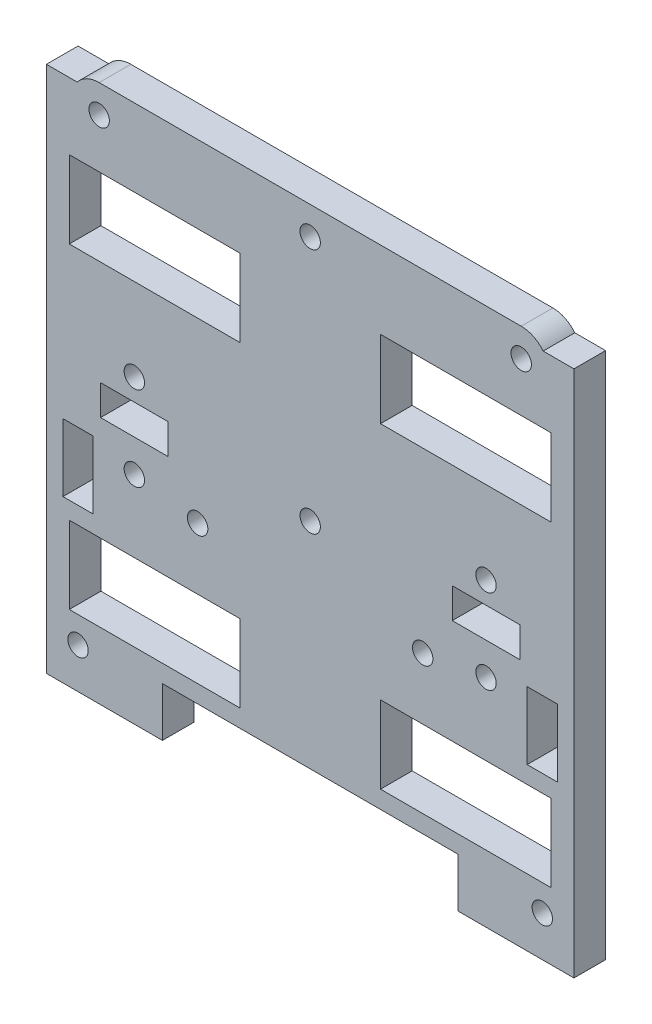
SolidWorks part; units mm, degrees
ref_plane "Front Plane" through (0, 0, 0) normal (0, 0, 1) x (1, 0, 0)
ref_plane "Top Plane" through (0, 0, 0) normal (0, 1, 0) x (1, 0, 0)
ref_plane "Right Plane" through (0, 0, 0) normal (1, 0, 0) x (0, 0, -1)
sketch "Sketch1" plane through (0, 0, 0) normal (0, 0, 1) x (1, 0, 0)
  line L0 (0, -37.5) -> (0, 37.5) construction
  line L1 (-47.5, -37.5) -> (47.5, -37.5)
  line L2 (-47.5, -37.5) -> (-47.5, 37.5)
  line L3 (-47.5, 37.5) -> (47.5, 37.5)
  line L4 (47.5, -37.5) -> (47.5, 37.5)
  line L5 (-47.5, -37.5) -> (47.5, 37.5) construction
  line L6 (-47.5, 37.5) -> (47.5, -37.5) construction
  line L7 (-47.5, 0) -> (47.5, 0) construction
  line L8 (-47.5, 22.5) -> (47.5, 22.5) construction
  line L9 (34.25, 17) -> (10, 28) construction
  line L10 (-34.25, 28) -> (-10, 28)
  line L11 (-34.25, 28) -> (-34.25, 17)
  line L12 (-34.25, 17) -> (-10, 17)
  line L13 (-10, 28) -> (-10, 17)
  line L14 (-34.25, 28) -> (-10, 17) construction
  line L15 (-34.25, 17) -> (-10, 28) construction
  line L16 (34.25, 28) -> (10, 17) construction
  line L17 (10, 28) -> (10, 17)
  line L18 (34.25, 17) -> (10, 17)
  line L19 (34.25, 28) -> (34.25, 17)
  line L20 (34.25, 28) -> (10, 28)
  line L21 (34.25, -28) -> (10, -17) construction
  line L22 (-34.25, -17) -> (-10, -28) construction
  line L23 (-34.25, -28) -> (-10, -17) construction
  line L24 (34.25, -17) -> (10, -28) construction
  line L25 (34.25, -28) -> (10, -28)
  line L26 (34.25, -28) -> (34.25, -17)
  line L27 (34.25, -17) -> (10, -17)
  line L28 (10, -28) -> (10, -17)
  line L29 (-10, -28) -> (-10, -17)
  line L30 (-34.25, -17) -> (-10, -17)
  line L31 (-34.25, -28) -> (-34.25, -17)
  line L32 (-34.25, -28) -> (-10, -28)
  point P0 (0, 0)
  point P12 (-22.125, 22.5)
  point P21 (22.125, 22.5)
  point P30 (22.125, -22.5)
  point P31 (-22.125, -22.5)
  dimension "D1" = 95
  dimension "D2" = 75
  dimension "D3" = 22.5
  dimension "D4" = 24.25
  dimension "D5" = 11
  dimension "D6" = 10
extrude "Boss-Extrude1" add sketch "Sketch1" along normal blind 4.5
sketch "Sketch8" plane through (0, 0, 4.5) normal (0, 0, 1) x (1, 0, 0)
  line L0 (-47.5, 37.5) -> (-47.5, -37.5) construction
  line L1 (47.5, -37.5) -> (47.5, 37.5) construction
  circle A0 centre (-47.5, 29.5) radius 8
  circle A1 centre (47.5, 29.5) radius 8
  dimension "D1" = 16
extrude "Boss-Extrude2" [suppressed] add sketch "Sketch8" against normal through all
sketch "Sketch2" plane through (0, 0, 4.5) normal (0, 0, 1) x (1, 0, 0)
  line L0 (0, -37.5) -> (0, 37.5) construction
  line L1 (-47.5, -37.5) -> (47.5, -37.5) construction
  line L2 (47.5, 37.5) -> (-47.5, 37.5) construction
  line L3 (-47.5, 0) -> (47.5, 0) construction
  line L4 (-47.5, 37.5) -> (-47.5, -37.5) construction
  line L5 (47.5, -37.5) -> (47.5, 37.5) construction
  line L6 (-40, 0) -> (40, 0) construction
  line L7 (-30, 35) -> (30, 35) construction
  circle A0 centre (-30, 35) radius 1.45
  circle A1 centre (30, 35) radius 1.45
  circle A2 centre (40, 0) radius 1.45
  circle A3 centre (-40, 0) radius 1.45
  circle A4 centre (0, 35) radius 1.45
  dimension "D1" = 2.9
  dimension "D7" = 2.9
  dimension "D8" = 2.9
  dimension "D9" = 2.9
  dimension "D2" = 30
  dimension "D3" = 35
  dimension "D4" = 80
  dimension "D5" = 40
  dimension "D6" = 0
extrude "screwHoles" cut sketch "Sketch2" against normal through all
sketch "Sketch3" plane through (0, 0, 4.5) normal (0, 0, 1) x (1, 0, 0)
  line L0 (-47.5, -20) -> (26.0486, -20) construction
  line L1 (-47.5, 37.5) -> (-47.5, -37.5) construction
  line L3 (0, 37.5) -> (0, -37.5) construction
  line L4 (47.5, 37.5) -> (-47.5, 37.5) construction
  line L5 (-47.5, -37.5) -> (47.5, -37.5) construction
  line L6 (18.95, -22.2) -> (9.05, -17.8) construction
  line L7 (-18.95, -17.8) -> (-9.05, -17.8)
  line L8 (-18.95, -17.8) -> (-18.95, -22.2)
  line L9 (-18.95, -22.2) -> (-9.05, -22.2)
  line L10 (-9.05, -17.8) -> (-9.05, -22.2)
  line L11 (-18.95, -17.8) -> (-9.05, -22.2) construction
  line L12 (-18.95, -22.2) -> (-9.05, -17.8) construction
  line L13 (18.95, -17.8) -> (9.05, -22.2) construction
  line L14 (9.05, -17.8) -> (9.05, -22.2)
  line L15 (18.95, -22.2) -> (9.05, -22.2)
  line L16 (18.95, -17.8) -> (18.95, -22.2)
  line L17 (18.95, -17.8) -> (9.05, -17.8)
  line L18 (-47.5, 37.5) -> (-47.5, -37.5) construction
  point P2 (-47.5, 0)
  point P12 (-14, -20)
  point P21 (14, -20)
  dimension "D1" = 9.9
  dimension "D2" = 4.4
  dimension "D3" = 14
  dimension "D4" = 20
extrude "BeltClamp" [suppressed] cut sketch "Sketch3" against normal through all
sketch "Sketch4" plane through (0, 0, 4.5) normal (0, 0, 1) x (1, 0, 0)
  line L0 (-47.5, 0) -> (47.5, 0) construction
  line L1 (-47.5, 37.5) -> (-47.5, -37.5) construction
  line L2 (47.5, -37.5) -> (47.5, 37.5) construction
  line L3 (0, 0) -> (0, 33.55) construction
  line L4 (-29.8, 2.15) -> (-20.2, 2.15)
  line L5 (-29.8, 2.15) -> (-29.8, -2.15)
  line L6 (-29.8, -2.15) -> (-20.2, -2.15)
  line L7 (-20.2, 2.15) -> (-20.2, -2.15)
  line L8 (-29.8, 2.15) -> (-20.2, -2.15) construction
  line L9 (-29.8, -2.15) -> (-20.2, 2.15) construction
  line L10 (29.8, -2.15) -> (20.2, 2.15) construction
  line L11 (29.8, 2.15) -> (20.2, -2.15) construction
  line L12 (20.2, 2.15) -> (20.2, -2.15)
  line L13 (29.8, -2.15) -> (20.2, -2.15)
  line L14 (29.8, 2.15) -> (29.8, -2.15)
  line L15 (29.8, 2.15) -> (20.2, 2.15)
  line L16 (-29.8, -2.15) -> (-20.2, 2.15) construction
  circle A0 centre (-40, 0) radius 1.45 construction
  circle A1 centre (0, 35) radius 1.45 construction
  circle A2 centre (0, 0) radius 1.45
  point P6 (-25, 0)
  point P22 (25, 0)
  dimension "D5" = 2.9
  dimension "D3" = 0
  dimension "D1" = 9.6
  dimension "D2" = 4.3
  dimension "D4" = 25
extrude "Cut-Extrude3" cut sketch "Sketch4" against normal through all
sketch "Sketch5" plane through (0, 0, 4.5) normal (0, 0, 1) x (1, 0, 0)
  line L0 (-47.5, -9.75) -> (47.5, -9.75) construction
  line L1 (-47.5, 37.5) -> (-47.5, -37.5) construction
  line L2 (47.5, -37.5) -> (47.5, 37.5) construction
  line L4 (0, -37.5) -> (0, 37.5) construction
  line L5 (-47.5, -37.5) -> (47.5, -37.5) construction
  line L6 (47.5, 37.5) -> (-47.5, 37.5) construction
  line L7 (-30.85, -14.55) -> (-35.15, -4.95) construction
  line L8 (30.85, -4.95) -> (35.15, -4.95)
  line L9 (30.85, -4.95) -> (30.85, -14.55)
  line L10 (30.85, -14.55) -> (35.15, -14.55)
  line L11 (35.15, -4.95) -> (35.15, -14.55)
  line L12 (30.85, -4.95) -> (35.15, -14.55) construction
  line L13 (30.85, -14.55) -> (35.15, -4.95) construction
  line L14 (-30.85, -4.95) -> (-35.15, -14.55) construction
  line L15 (-35.15, -4.95) -> (-35.15, -14.55)
  line L16 (-30.85, -14.55) -> (-35.15, -14.55)
  line L17 (-30.85, -4.95) -> (-30.85, -14.55)
  line L18 (-30.85, -4.95) -> (-35.15, -4.95)
  line L19 (33, -9.75) -> (33, -37.5) construction
  line L20 (-33, -9.75) -> (-33, -37.5) construction
  line L21 (-33, -31.75) -> (33, -31.75) construction
  circle A0 centre (33, -31.75) radius 1.45
  circle A1 centre (-33, -31.75) radius 1.45
  point P15 (33, -9.75)
  point P24 (-33, -9.75)
  dimension "D5" = 2.9
  dimension "D2" = 9.6
  dimension "D3" = 4.3
  dimension "D4" = 33
  dimension "D6" = 22
  dimension "D1" = 9.75
extrude "Cut-Extrude4" cut sketch "Sketch5" against normal through all
sketch "Sketch9" plane through (0, 0, 4.5) normal (0, 0, 1) x (1, 0, 0)
  line L0 (47.5, 37.5) -> (-47.5, 37.5) construction
  line L1 (0, 37.5) -> (0, -37.5) construction
  line L2 (-47.5, -37.5) -> (47.5, -37.5) construction
  line L3 (50.5, 35) -> (45.5, 35) construction
  line L4 (-50.5, 35) -> (-45.5, 35) construction
  circle A0 centre (-30, 35) radius 4
  circle A1 centre (-30, 35) radius 1.45
  circle A2 centre (-30, 35) radius 1.45 construction
  circle A3 centre (30, 35) radius 1.45
  circle A4 centre (30, 35) radius 4
  point P17 (0, -37.5)
  dimension "D1" = 8
extrude "Boss-Extrude3" add sketch "Sketch9" against normal through all
sketch "Sketch10" plane through (0, 0, 4.5) normal (0, 0, 1) x (1, 0, 0)
  line L0 (-60, 37.5) -> (-37.5, 37.5)
  line L1 (-37.5, 37.5) -> (-37.5, -37.5)
  line L2 (-47.5, -37.5) -> (47.5, -37.5) construction
  line L3 (-37.5, -37.5) -> (-60, -37.5)
  line L4 (-60, -37.5) -> (-60, 37.5)
  line L5 (0, 37.5) -> (0, -37.5) construction
  line L6 (26.8775, 37.5) -> (-26.8775, 37.5) construction
  line L7 (60, -37.5) -> (60, 37.5)
  line L8 (37.5, -37.5) -> (60, -37.5)
  line L9 (37.5, 37.5) -> (37.5, -37.5)
  line L10 (60, 37.5) -> (37.5, 37.5)
  line L11 (-60, -37.5) -> (-60, 37.5)
  line L12 (-33.1225, 37.5) -> (-47.5, 37.5) construction
  line M3 (47.5, -37.5) -> (47.5, 37.5)
  line M7 (-47.5, 37.5) -> (-47.5, -37.5)
  line M8 (-47.5, -37.5) -> (47.5, -37.5)
  dimension "D3" = 0
  dimension "D1" = 75
  dimension "D2" = 60
extrude "Cut-Extrude5" cut sketch "Sketch10" against normal through all contours L1 L0 M7 M8 | L10 L9 M3 M8 region at (42.5, 0, 4.5) region at (-42.5, 0, 4.5)
sketch "Sketch11" plane through (0, 0, 4.5) normal (0, 0, 1) x (1, 0, 0)
  line L0 (-30, 39) -> (30, 39)
  line L1 (30, 39) -> (26.8775, 37.5)
  line L2 (26.8775, 37.5) -> (-26.8775, 37.5)
  line L3 (-26.8775, 37.5) -> (-30, 39)
  arc A0 (-26.8775, 37.5) -> (-33.1225, 37.5) centre (-30, 35) ccw construction
  arc A1 (33.1225, 37.5) -> (26.8775, 37.5) centre (30, 35) ccw construction
extrude "Boss-Extrude4" add sketch "Sketch11" against normal through all
sketch "Sketch12" plane through (0, 0, 4.5) normal (0, 0, 1) x (1, 0, 0)
  line L0 (-37.5, -8.25) -> (37.5, -8.25) construction
  line L1 (-37.5, 37.5) -> (-37.5, -37.5) construction
  line L2 (37.5, 37.5) -> (37.5, -37.5) construction
  line L3 (0, 0) -> (0, -37.5) construction
  line L4 (-37.5, -37.5) -> (37.5, -37.5) construction
  circle A0 centre (-16, -8.25) radius 1.45
  circle A1 centre (16, -8.25) radius 1.45
  dimension "D2" = 2.9
  dimension "D1" = 16
  dimension "D3" = 8.25
extrude "FanBraceScrews" cut sketch "Sketch12" against normal through all
sketch "Sketch13" plane through (0, 0, 4.5) normal (0, 0, 1) x (1, 0, 0)
  line L0 (-37.5, -37.5) -> (37.5, -37.5) construction
  line L1 (-21, -44.5) -> (21, -44.5)
  line L2 (-21, -44.5) -> (-21, -30.5)
  line L3 (-21, -30.5) -> (21, -30.5)
  line L4 (21, -44.5) -> (21, -30.5)
  line L5 (-21, -44.5) -> (21, -30.5) construction
  line L6 (-21, -30.5) -> (21, -44.5) construction
  point P0 (0, -37.5)
  dimension "D1" = 42
  dimension "D2" = 7
extrude "Cut-Extrude7" cut sketch "Sketch13" against normal through all
sketch "Sketch14" plane through (0, 0, 4.5) normal (0, 0, 1) x (1, 0, 0)
  line L0 (16, -9.7) -> (16, 3.75) construction
  line L1 (0, 0) -> (0, -40.3958) construction
  line L2 (-16, -9.7) -> (-16, 3.75) construction
  circle A0 centre (16, -8.25) radius 1.45 construction
  circle A1 centre (16, 3.75) radius 1.45
  circle A2 centre (-16, 3.75) radius 1.45
  dimension "D2" = 2.9
  dimension "D1" = 12
extrude "Cut-Extrude8" [suppressed] cut sketch "Sketch14" against normal through all
sketch "Sketch15" plane through (0, 0, 4.5) normal (0, 0, 1) x (1, 0, 0)
  line L0 (-25, 5.25) -> (-25, -6.75) construction
  line L2 (0, 0) -> (0, -11.0705) construction
  line L3 (16, -8.3509) -> (25, -6.75) construction
  line L4 (25, 5.25) -> (25, -6.75) construction
  circle A0 centre (-25, 5.25) radius 1.45
  circle A1 centre (-25, -6.75) radius 1.45
  circle A2 centre (25, -6.75) radius 1.45
  circle A3 centre (25, 5.25) radius 1.45
  circle A5 centre (-16, -8.25) radius 1.45 construction
  dimension "D1" = 12
  dimension "D3" = 2.9
  dimension "D4" = 2.9
  dimension "D2" = 25
  dimension "D5" = 1.5
extrude "BeltClipScrews" cut sketch "Sketch15" against normal through all
sketch "Sketch16" [suppressed] plane through (0, 0, 4.5) normal (0, 0, 1) x (1, 0, 0)
  line L0 (0, 0) -> (0, -11.3016) construction
  line L1 (-30.1, 2.35) -> (-19.9, 2.35)
  line L2 (-30.1, 2.35) -> (-30.1, -2.35)
  line L3 (-30.1, -2.35) -> (-19.9, -2.35)
  line L4 (-19.9, 2.35) -> (-19.9, -2.35)
  line L5 (-35.35, -4.65) -> (-30.65, -4.65)
  line L6 (-35.35, -4.65) -> (-35.35, -14.85)
  line L7 (-35.35, -14.85) -> (-30.65, -14.85)
  line L8 (-30.65, -4.65) -> (-30.65, -14.85)
  line L9 (30.65, -4.65) -> (30.65, -14.85)
  line L10 (35.35, -14.85) -> (30.65, -14.85)
  line L11 (35.35, -4.65) -> (35.35, -14.85)
  line L12 (35.35, -4.65) -> (30.65, -4.65)
  line L13 (19.9, 2.35) -> (19.9, -2.35)
  line L14 (30.1, -2.35) -> (19.9, -2.35)
  line L15 (30.1, 2.35) -> (30.1, -2.35)
  line L16 (30.1, 2.35) -> (19.9, 2.35)
  line L17 (-30.65, -4.65) -> (-30.65, -14.85)
extrude "Boss-Extrude5" [suppressed] add sketch "Sketch16" against normal through all contours L8 L5 L6 L7 | L4 L1 L2 L3 | L15 L16 L13 L14 | L11 L12 L9 L10
equation "\"X-ROD-SPACING\"=45"
equation "\"Y-ROD-SPACING\"=75"
equation "\"Z-ROD-SPACING\"=17.5"
equation "\"Y-BED-OFFSET\"=2"
equation "\"Y-BED-ROD-INSET\"=3.5"
equation "\"Y-BED-SCREW-SPACING\"=209"
equation "\"Y-BED-SCREW-CUTOUT-SLOT-HEIGHT\"=2"
equation "\"T-SLOT-NUT-FILLET-RADIUS\"=0.5"
equation "\"T-SLOT-SCREW-SHAFT-RADIUS\"=1.55"
equation "\"T-SLOT-SCREW-SHAFT-CUTOUT-LENGTH\"=11.0"
equation "\"T-SLOT-NUT-DEPTH\"=3.5"
equation "\"T-SLOT-NUT-WIDTH\"=2.85"
equation "\"T-SLOT-NUT-END-DISTANCE\"=8"
equation "\"ACRYLIC-THICKNESS\"=10"
equation "\"ACRYLIC-THICKNESS2\"=4.5"
equation "\"ACRYLIC-TAB-CUTOUT-SIZE\"=\"ACRYLIC-THICKNESS\"+\"ACRYLIC-TAB-TOLERANCE\"*2"
equation "\"ACRYLIC-TAB-WIDTH\"=\"ACRYLIC-THICKNESS\""
equation "\"ACRYLIC-M3-HOLE\"=2.9"
equation "\"SMOOTHROD-CAP-SCREW-DISTANCE\"=20"
equation "\"FRAME-WIDTH-INNER\"=370"
equation "\"NEMA17-HOLE-SPACING\"=31"
equation "\"NEMA17-CENTRAL-CUTOUT\"=22.5"
equation "\"Z-BRACKET-REACH\"=55"
equation "\"Z-ROD-INSET\"=16"
equation "\"TOP-BRACKET-SPACING\"=40"
equation "\"SMOOTHROD-X-LENGTH\"=350"
equation "\"SMOOTHROD-Y-LENGTH\"=350"
equation "\"SMOOTHROD-Z-LENGTH\"=350"
equation "\"SMOOTHROD-TIGHTENING-HEADROOM\"=.25"
equation "\"LEADSCREW-Z-LENGTH\"=300"
equation "\"SCREW-LENGTH-FRAME\"=\"ACRYLIC-THICKNESS\" + 10"
equation "\"SCREW-LENGTH-MOTOR\"=\"ACRYLIC-THICKNESS\" + 5"
equation "\"SCREW-HEAD-RADIUS\"=6"
equation "\"PRINTED-X-SMOOTHROD-DIAMETER\"=9.0"
equation "\"PRINTED-X-SMOOTHROD-CUTOUT\"=10"
equation "\"PRINTED-X-BASE-HEIGHT\"=10"
equation "\"PRINTED-LM8UU-CUTOUT-SIZE\"=15.5"
equation "\"PRINTED-LM8UU-CUTOUT-LENGTH\"=24.5"
equation "\"PRINTED-X-IDLER-HEIGHT\"=16"
equation "\"PSU-MOUNTING-WIDTH\"=95"
equation "\"PSU-MOUNTING-HEIGHT\"=177"
equation "\"Y-BELT-TO-ROD-DISTANCE\"=20"
equation "\"SPOOL-HOLDER-ROD-SPACING\"=150"
equation "\"D3@Sketch1\"=\"X-ROD-SPACING\"/2"
equation "\"D4@Sketch1\"=\"ACRYLIC-X-CARRIAGE-LM8UU-CUTOUT-WIDTH\""
equation "\"D1@Boss-Extrude1\"=\"ACRYLIC-THICKNESS2\""
equation "\"D1@Sketch2\"=\"ACRYLIC-M3-HOLE\""
equation "\"D1@Sketch3\"=\"ACRYLIC-TAB-CUTOUT-SIZE\""
equation "\"D2@Sketch3\"=\"ACRYLIC-THICKNESS2\"+\"ACRYLIC-TAB-TOLERANCE\"*2"
equation "\"ACRYLIC-X-CARRIAGE-WIDTH\"=55"
equation "\"ACRYLIC-X-CARRIAGE-HEIGHT\"=75"
equation "\"D2@Sketch1\"=\"ACRYLIC-X-CARRIAGE-HEIGHT\""
equation "\"ACRYLIC-X-CARRIAGE-CENTER-TAB-SPACING\"=14"
equation "\"D3@Sketch3\"=\"ACRYLIC-X-CARRIAGE-CENTER-TAB-SPACING\""
equation "\"SCREW-LENGTH-EXTRUDER\"=28"
equation "\"ACRYLIC-X-CARRIAGE-SCREW-SPACING-X\"=15"
equation "\"ACRYLIC-X-CARRIAGE-SCREW-SPACING-Y\"=33"
equation "\"D1@Sketch4\"=\"ACRYLIC-TAB-WIDTH\"-\"KERF\"*4"
equation "\"D2@Sketch4\"=\"ACRYLIC-THICKNESS2\"-\"KERF\"*2"
equation "\"D2@Sketch5\"=\"ACRYLIC-TAB-WIDTH\"-\"KERF\"*4"
equation "\"D3@Sketch5\"=\"ACRYLIC-THICKNESS2\"-\"KERF\"*2"
equation "\"ACRYLIC-X-CARRIAGE-EXTRUDER-SHELF-DEPTH\"=\"ACRYLIC-X-CARRIAGE-EXTRUDER-OFFSET\" + 28"
equation "\"ACRYLIC-X-CARRIAGE-EXTRUDER-BRACE-SPACING\"=23"
equation "\"D4@Sketch5\"=\"ACRYLIC-X-CARRIAGE-DUAL-MOUNT-BRACE-WIDTH\""
equation "\"D1@Sketch5\"=\"ACRYLIC-THICKNESS2\"/2 + 7.5"
equation "\"D4@Sketch2\"=\"ACRYLIC-X-CARRIAGE-DUAL-MOUNT-SCREW-WIDTH\"*2"
equation "\"D5@Sketch2\"=\"ACRYLIC-X-CARRIAGE-DUAL-MOUNT-SCREW-WIDTH\""
equation "\"D7@Sketch2\"=\"ACRYLIC-M3-HOLE\""
equation "\"D8@Sketch2\"=\"ACRYLIC-M3-HOLE\""
equation "\"ACRYLIC-X-CARRIAGE-LM8UU-CUTOUT-WIDTH\"=24.25"
equation "\"ACRYLIC-TAB-TOLERANCE\"=-.05"
equation "\"ACRYLIC-X-CARRIAGE-EXTRUDER-OFFSET\"=26"
equation "\"ACRYLIC-X-CARRIAGE-EXTRUDER-ANGLE\"=90"
equation "\"ACRYLIC-X-CARRIAGE-EXTRUDER-BRACE-TAB-OFFSET\"=20"
equation "\"ACRYLIC-X-CARRIAGE-EXTRUDER-BRACE-HEIGHT\"=35"
equation "\"ACRYLIC-X-CARRIAGE-EXTRUDER-BRACE-SCREW-SPACING\"=22"
equation "\"D5@Sketch5\"=\"ACRYLIC-M3-HOLE\""
equation "\"ACRYLIC-X-CARRIAGE-DUAL-WIDTH-MULTIPLIER\"=1.65"
equation "\"ACRYLIC-X-CARRIAGE-DUAL-HOTEND-SPACING\"=42"
equation "\"ACRYLIC-X-CARRIAGE-DUAL-WIDTH\"=75"
equation "\"ACRYLIC-X-CARRIAGE-DUAL-HOTEND-SEPARATION\"=36"
equation "\"ACRYLIC-X-CARRIAGE-DUAL-MOUNT-PLATE-DEPTH\"=75"
equation "\"ACRYLIC-X-CARRIAGE-DUAL-MOUNT-BRACE-WIDTH\"=33"
equation "\"ACRYLIC-X-CARRIAGE-DUAL-MOUNT-SCREW-WIDTH\"=40"
equation "\"D9@Sketch2\"=\"ACRYLIC-M3-HOLE\""
equation "\"ACRYLIC-X-CARRIAGE-LM8UU-CUTOUT-HEIGHT\"=11.0"
equation "\"D5@Sketch1\"=\"ACRYLIC-X-CARRIAGE-LM8UU-CUTOUT-HEIGHT\""
equation "\"D1@Sketch10\"=\"ACRYLIC-X-CARRIAGE-DUAL-WIDTH\""
equation "\"D5@Sketch4\"=\"ACRYLIC-M3-HOLE\""
equation "\"D2@Sketch12\"=\"ACRYLIC-M3-HOLE\""
equation "\"D3@Sketch12\"=\"ACRYLIC-THICKNESS2\"/2 + 6"
equation "\"D2@Sketch14\"=\"ACRYLIC-M3-HOLE\""
equation "\"D3@Sketch15\"=\"ACRYLIC-M3-HOLE\""
equation "\"D4@Sketch15\"=\"ACRYLIC-M3-HOLE\""
equation "\"KERF\"=0.1"
equation "\"ACRYLIC-THICKNESS-TAB-CUTOUT-WIDTH\"=\"ACRYLIC-THICKNESS\"-\"KERF\"*2"
equation "\"ACRYLIC-THICKNESS-TAB-CUTOUT-HEIGHT\"=\"ACRYLIC-TAB-WIDTH\"-\"KERF\"*4"
equation "\"ACRYLIC-THICKNESS2-TAB-CUTOUT-WIDTH\"=\"ACRYLIC-THICKNESS2\"-\"KERF\"*2"
equation "\"ACRYLIC-THICKNESS2-TAB-CUTOUT-HEIGHT\"=\"ACRYLIC-TAB-WIDTH\"-\"KERF\"*4"
equation "\"PRINTED-M3-HOLE\"=3.5"
equation "\"PRINTED-M3-NUT-AF\"=6.25"
equation "\"ACRYLIC-X-CARRIAGE-DUAL-FAN-OFFSET\"=52"
equation "\"ACRYLIC-X-CARRIAGE-DUAL-FAN-HEIGHT\"=20"
equation "\"BLOWER-FAN-WIDTH\"=15"
